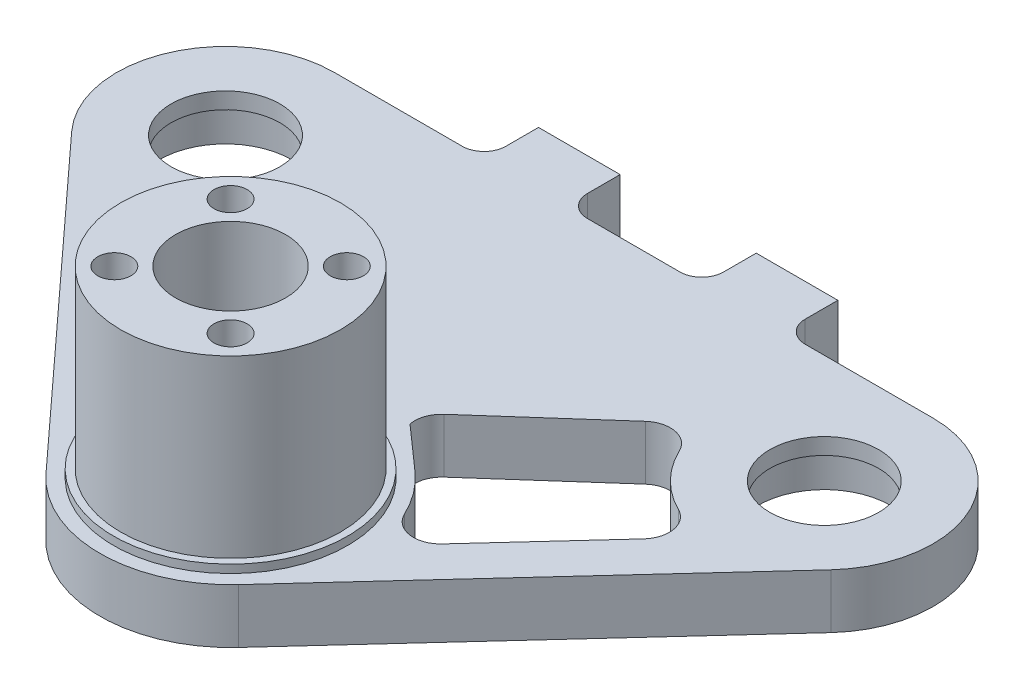
SolidWorks part; units mm, degrees
material "PLA Infill"
ref_plane "Front Plane" through (0, 0, 0) normal (0, 0, 1) x (1, 0, 0)
ref_plane "Top Plane" through (0, 0, 0) normal (0, 1, 0) x (1, 0, 0)
ref_plane "Right Plane" through (0, 0, 0) normal (1, 0, 0) x (0, 0, -1)
sketch "Sketch1" plane through (0, 0, 0) normal (0, 1, 0) x (1, 0, 0)
  line L0 (0, 0) -> (55, 54.0672) construction
  line L1 (55, 54.0672) -> (-55, 54.0672) construction
  line L2 (-55, 54.0672) -> (0, 0) construction
  line L3 (-69.7415, 40.551) -> (-17.6898, -16.2194)
  line L4 (-41.7379, 69.0378) -> (15.9145, 17.9646)
  line L5 (-47.6255, 28.2677) -> (-29.9271, 8.9649)
  line L6 (-29.0781, 47.135) -> (-9.4754, 29.7694)
  circle A0 centre (0, 0) radius 10.1
  circle A1 centre (-55, 54.0672) radius 10
  circle A2 centre (0, 0) radius 24 construction
  circle A3 centre (-55, 54.0672) radius 20 construction
  arc A4 (-69.7415, 40.551) -> (-41.7379, 69.0378) centre (-55, 54.0672) cw
  arc A5 (-17.6898, -16.2194) -> (15.9145, 17.9646) centre (0, 0) ccw
  arc A6 (-46.1521, 36.1308) -> (-36.9149, 45.5274) centre (-55, 54.0672) ccw
  arc A7 (-21.7173, 10.2157) -> (-10.5856, 21.5394) centre (0, 0) cw
  arc A8 (-29.9271, 8.9649) -> (-21.7173, 10.2157) centre (-26.2417, 12.3439) ccw
  arc A9 (-9.4754, 29.7694) -> (-10.5856, 21.5394) centre (-12.7909, 26.0268) cw
  arc A10 (-29.0781, 47.135) -> (-36.9149, 45.5274) centre (-32.3936, 43.3924) ccw
  arc A11 (-47.6255, 28.2677) -> (-46.1521, 36.1308) centre (-43.9401, 31.6467) cw
  point P22 (-23.8825, 2.3723)
  point P25 (-2.7804, 23.8384)
  point P28 (-35.0663, 52.4399)
  point P31 (-53.032, 34.1643)
  dimension "D3" = 20.2
  dimension "D4" = 20
  dimension "D5" = 48
  dimension "D6" = 40
  dimension "D9" = 5
  dimension "D1" = 77.125
  dimension "D2" = 110
  dimension "D7" = 8
  dimension "D8" = 8
extrude "Main Body" add sketch "Sketch1" along normal blind 10
sketch "Sketch2" plane through (0, 0, 0) normal (0, -1, 0) x (1, 0, 0)
  circle A0 centre (-55, -54.0672) radius 10 construction
  circle A1 centre (-55, -54.0672) radius 10 construction
  circle A2 centre (-55, -54.0672) radius 12.2
  dimension "D1" = 24.4
extrude "Bearing Recess" cut sketch "Sketch2" against normal blind 7
sketch "Sketch3" plane through (0, 0, 0) normal (0, -1, 0) x (1, 0, 0)
  circle A0 centre (0, 0) radius 21.5
  circle A1 centre (0, 0) radius 10.1
  circle A2 centre (0, 0) radius 10.1 construction
  dimension "D1" = 43
extrude "Standoff Section" add sketch "Sketch3" along normal blind 1.5 and the other way blind 11.5
sketch "Sketch9" plane through (0, 10, 0) normal (0, 1, 0) x (1, 0, 0)
  circle A0 centre (0, 0) radius 20.2
  circle A1 centre (0, 0) radius 10.1
  dimension "D1" = 40.4
  dimension "D2" = 20.2
extrude "Boss-Extrude1" add sketch "Sketch9" along normal blind 33.7
ref_plane "Mirror Plane" through (0, 0, 0) normal (1, 0, 0) x (0, 0, -1)
sketch "Sketch6" plane through (0, 0, 0) normal (0, 1, 0) x (1, 0, 0)
  line L0 (-55, 74.0672) -> (0, 74.0672) construction
  line L1 (0, -24.86) -> (0, 24.86) construction
  line L2 (0, 74.0672) -> (0, 32.063)
  line L3 (-41.7379, 69.0378) -> (15.9145, 17.9646) construction
  line L4 (0, 32.063) -> (-41.7379, 69.0378)
  line L5 (-20, 84.0672) -> (-20, 74.0672) construction
  line L6 (-27.5, 74.0672) -> (-12.5, 74.0672) construction
  line L7 (-27.5, 78.0672) -> (-27.5, 84.0672)
  line L8 (-27.5, 84.0672) -> (-12.5, 84.0672)
  line L9 (-12.5, 78.0672) -> (-12.5, 84.0672)
  line L10 (-55, 74.0672) -> (-31.5, 74.0672)
  line L11 (-8.5, 74.0672) -> (0, 74.0672)
  arc A0 (-41.7379, 69.0378) -> (-69.7415, 40.551) centre (-55, 54.0672) ccw construction
  arc A1 (-41.7379, 69.0378) -> (-69.7415, 40.551) centre (-55, 54.0672) ccw construction
  arc A2 (-55, 74.0672) -> (-41.7379, 69.0378) centre (-55, 54.0672) cw
  arc A3 (-8.5, 74.0672) -> (-12.5, 78.0672) centre (-8.5, 78.0672) cw
  arc A4 (-31.5, 74.0672) -> (-27.5, 78.0672) centre (-31.5, 78.0672) ccw
  dimension "D4" = 4
  dimension "D1" = 10
  dimension "D2" = 20
  dimension "D3" = 15
extrude "Extra Geometry" add sketch "Sketch6" along normal blind 10
sketch "Sketch8" plane through (0, 0, -84.0672) normal (0, 0, -1) x (-1, 0, 0)
  line L0 (20, 10) -> (20, 0) construction
  line L1 (12.5, 10) -> (27.5, 10) construction
  line L2 (12.5, 0) -> (27.5, 0) construction
  circle A0 centre (20, 5) radius 2
  point P9 (20, 5)
  dimension "D1" = 4
extrude "Cut-Extrude1" cut sketch "Sketch8" against normal blind 6
mirror "Mirror2" about plane through (0, 0, 0) normal (1, 0, 0) of bodies 109 107
sketch "Sketch4" plane through (0, -1.5, 0) normal (0, -1, 0) x (1, 0, 0)
  line L0 (0, 0) -> (50000, 0) construction
  line L1 (55, -54.0672) -> (-55, -54.0672) construction
  line L2 (-10.6773, 10.6773) -> (0, 0) construction
  circle A0 centre (-10.6773, 10.6773) radius 3.05
  circle A2 centre (10.6773, 10.6773) radius 3.05
  circle A3 centre (10.6773, -10.6773) radius 3.05
  circle A4 centre (-10.6773, -10.6773) radius 3.05
  dimension "D1" = 6.1
  dimension "D2" = 15.1
  dimension "D3" = 45
  dimension "D4" = 4
extrude "M6 Bolt holes" cut sketch "Sketch4" against normal through all
